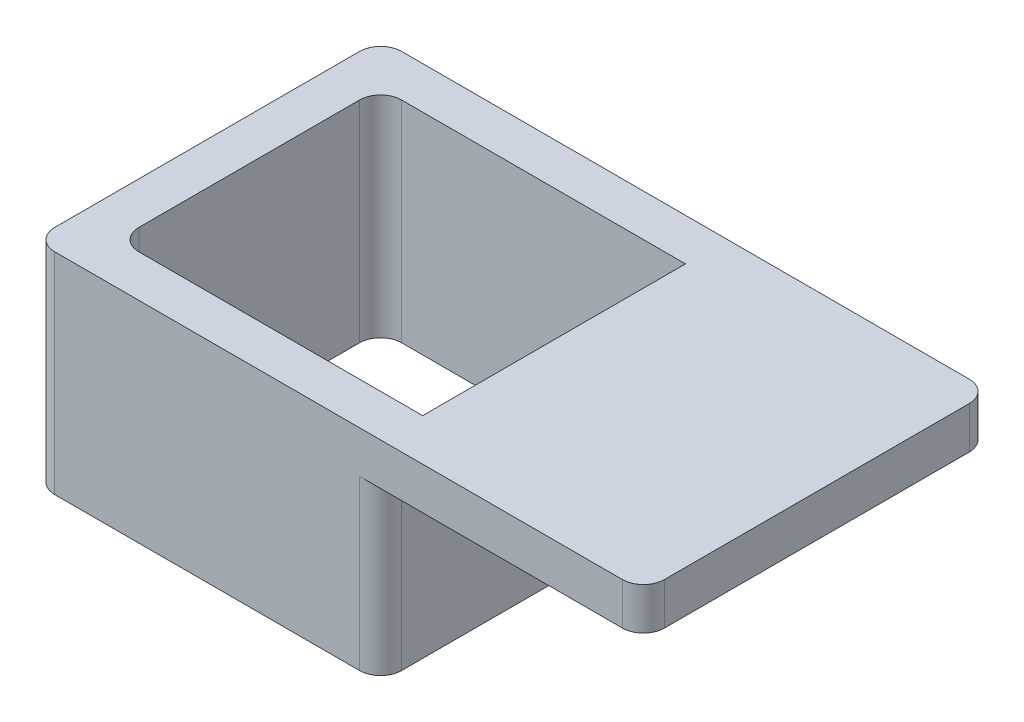
SolidWorks part; units mm, degrees
ref_plane "Alzado" through (0, 0, 0) normal (0, 0, 1) x (1, 0, 0)
ref_plane "Planta" through (0, 0, 0) normal (0, 1, 0) x (1, 0, 0)
ref_plane "Vista lateral" through (0, 0, 0) normal (1, 0, 0) x (0, 0, -1)
sketch "Croquis1" plane through (0, 0, 0) normal (0, 1, 0) x (1, 0, 0)
  line L1 (6.25, 6.25) -> (-6.25, 6.25)
  line L2 (6.25, 6.25) -> (6.25, -6.25)
  line L3 (6.25, -6.25) -> (-6.25, -6.25)
  line L4 (-6.25, 6.25) -> (-6.25, -6.25)
  line L5 (6.25, 6.25) -> (-6.25, -6.25) construction
  line L6 (6.25, -6.25) -> (-6.25, 6.25) construction
  line L7 (8.25, 8.25) -> (-8.25, 8.25)
  line L8 (8.25, 8.25) -> (8.25, -8.25)
  line L9 (8.25, -8.25) -> (-8.25, -8.25)
  line L10 (-8.25, 8.25) -> (-8.25, -8.25)
  line L11 (8.25, 8.25) -> (-8.25, -8.25) construction
  line L12 (8.25, -8.25) -> (-8.25, 8.25) construction
  point P0 (0, 0)
  point P6 (0, 0)
  dimension "D1" = 12.5
  dimension "D2" = 2
extrude "Saliente-Extruir1" add sketch "Croquis1" along normal blind 10
chamfer "Chaflán1" distance 2 angle 45 1 edges at (6.25, 10, 0)
sketch "Croquis2" plane through (8.25, 0, 0) normal (1, 0, 0) x (0, 0, -1)
  line L0 (8.25, 10) -> (8.25, 0) construction
  line L1 (-8.25, 10) -> (8.25, 10)
  line L2 (-8.25, 10) -> (-8.25, 8)
  line L3 (-8.25, 8) -> (8.25, 8)
  line L4 (8.25, 10) -> (8.25, 8)
  dimension "D1" = 2
extrude "Saliente-Extruir2" add sketch "Croquis2" along normal blind 12.5
fillet "Redondeo1" radius 1 8 edges at (20.75, 9, -8.25) (20.75, 9, 8.25) (8.25, 4, 8.25) (8.25, 4, -8.25) (-8.25, 5, -8.25) (-8.25, 5, 8.25) (-6.25, 5, 6.25) (-6.25, 5, -6.25)
